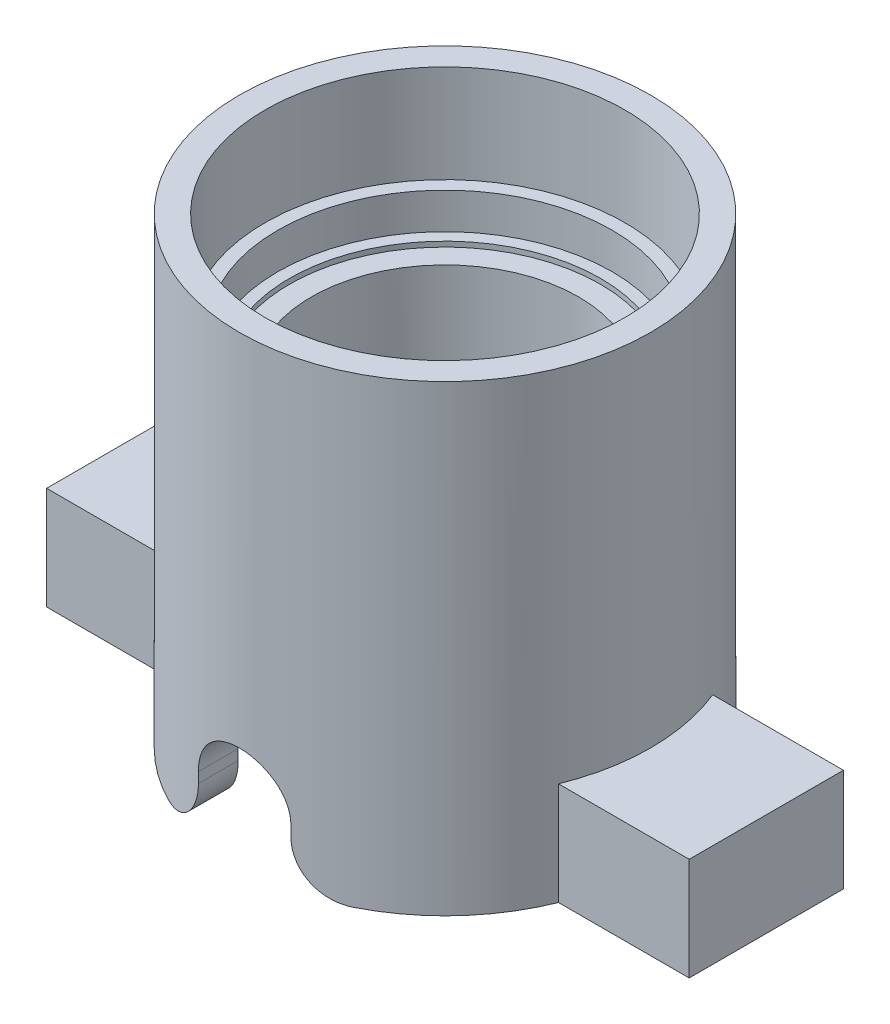
SolidWorks part; units mm, degrees
ref_plane "Front Plane" through (0, 0, 0) normal (0, 0, 1) x (1, 0, 0)
ref_plane "Top Plane" through (0, 0, 0) normal (0, 1, 0) x (1, 0, 0)
ref_plane "Right Plane" through (0, 0, 0) normal (1, 0, 0) x (0, 0, -1)
sketch "Sketch1" plane through (0, 0, 0) normal (0, 1, 0) x (1, 0, 0)
  line L1 (-50, 40) -> (50, 40)
  line L2 (-50, 40) -> (-50, -40)
  line L3 (-50, -40) -> (50, -40)
  line L4 (50, 40) -> (50, -40)
  line L5 (-50, 40) -> (50, -40) construction
  line L6 (-50, -40) -> (50, 40) construction
  circle A1 centre (0, 0) radius 26
  circle A2 centre (0, 0) radius 40
  point P0 (0, 0)
  dimension "D3" = 52
  dimension "D1" = 80
  dimension "D2" = 100
extrude "Boss-Extrude1" add sketch "Sketch1" along normal blind 70 contours A2 A1 region at (27.4843, 0, -27.4843)
sketch "Sketch2" plane through (0, 70, 0) normal (0, 1, 0) x (1, 0, 0)
  circle A0 centre (0, 0) radius 32.5
  dimension "D1" = 65
extrude "Cut-Extrude1" cut sketch "Sketch2" against normal blind 27
sketch "Sketch4" plane through (0, 43, 0) normal (0, 1, 0) x (1, 0, 0)
  circle A0 centre (0, 0) radius 30.25
  circle M3 centre (0, 0) radius 32.5
  dimension "D1" = 60.5
extrude "Boss-Extrude2" add sketch "Sketch4" along normal blind 1 contours A0 M3 region at (-31.5808, 43, 0)
sketch "Sketch5" plane through (0, 70, 0) normal (0, 1, 0) x (1, 0, 0)
  circle A0 centre (0, 0) radius 35
  dimension "D1" = 70
extrude "Cut-Extrude2" cut sketch "Sketch5" against normal offset from surface (19 mm away) 7 up to face at (0, 44, 30.25)
sketch "Sketch6" plane through (0, 0, 0) normal (0, -1, 0) x (1, 0, 0)
  circle A0 centre (0, 0) radius 32.5
  dimension "D1" = 65
extrude "Cut-Extrude3" cut sketch "Sketch6" against normal blind 8
sketch "Sketch7" plane through (0, 8, 0) normal (0, -1, 0) x (1, 0, 0)
  circle A0 centre (0, 0) radius 30.25
  dimension "D1" = 60.5
extrude "Cut-Extrude4" cut sketch "Sketch7" against normal blind 1
sketch "Sketch8" plane through (0, 0, 0) normal (0, -1, 0) x (-1, 0, 0)
  line L0 (0, 0) -> (63.4557, 0) construction
  line L1 (9, -48.771) -> (-9, -48.771)
  line L2 (9, -48.771) -> (9, -31.229)
  line L3 (9, -31.229) -> (-9, -31.229)
  line L4 (-9, -48.771) -> (-9, -31.229)
  line L5 (9, -48.771) -> (-9, -31.229) construction
  line L6 (9, -31.229) -> (-9, -48.771) construction
  line L7 (63.4557, 0) -> (-83.5837, 0) construction
  line L8 (0, 0) -> (0, 18.862) construction
  line L9 (62.5, 15) -> (32.5, 15)
  line L10 (62.5, 15) -> (62.5, -15)
  line L11 (62.5, -15) -> (32.5, -15)
  line L12 (32.5, 15) -> (32.5, -15)
  line L13 (62.5, 15) -> (32.5, -15) construction
  line L14 (62.5, -15) -> (32.5, 15) construction
  line L15 (-62.5, -15) -> (-32.5, -15)
  line L16 (-32.5, 15) -> (-32.5, -15)
  line L17 (-62.5, 15) -> (-32.5, 15)
  line L18 (-62.5, 15) -> (-62.5, -15)
  circle A0 centre (0, 0) radius 32.5
  circle A1 centre (0, 0) radius 40
  point P4 (0, -40)
  point P11 (47.5, 0)
  circle M2 centre (0, 0) radius 32.5
  circle M3 centre (0, 0) radius 40
  dimension "D2" = 65
  dimension "D3" = 80
  dimension "D1" = 18
  dimension "D4" = 30
  dimension "D5" = 30
extrude "Boss-Extrude3" add sketch "Sketch8" along normal blind 20 contours L17 L16 L12 L9 M3 M2 | L17 L15 L16 M3 | L16 L15 L4 M2 M3 | L17 L18 L15 M3 | L9 L12 L11 M3 | L11 L10 L9 M3 | L12 L2 L11 M2 M3 region at (-23.2683, 0, 25.937) region at (23.2683, 0, 25.937) region at (-50.7549, 0, 0) region at (-35.8281, 0, 0) region at (35.8281, 0, 0) region at (50.7549, 0, 0) region at (0, 0, -33.3426)
fillet "Fillet1" radius 9 4 edges at (9, -20, 35.1017) (-9, -20, 35.1017) (9, 0, 35.1017) (-9, 0, 35.1017)
